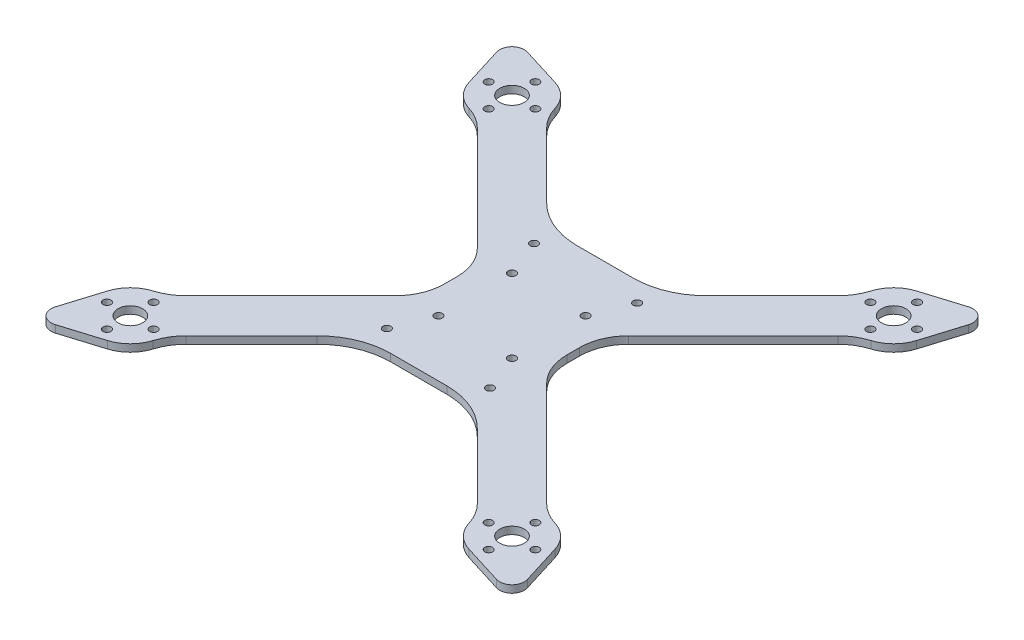
SolidWorks part; units mm, degrees
ref_plane "Front Plane" through (0, 0, 0) normal (0, 0, 1) x (1, 0, 0)
ref_plane "Top Plane" through (0, 0, 0) normal (0, 1, 0) x (1, 0, 0)
ref_plane "Right Plane" through (0, 0, 0) normal (1, 0, 0) x (0, 0, -1)
sketch "Sketch1" plane through (0, 0, 0) normal (0, 1, 0) x (1, 0, 0)
  line L0 (0, 110) -> (0, -110) construction
  line L1 (0, 0) -> (-77.7817, -77.7817) construction
  line L2 (0, 0) -> (-77.7817, 77.7817) construction
  line L3 (-77.7817, -77.7817) -> (-98.9949, -98.9949) construction
  line L4 (-11.4315, 38) -> (11.4315, 38)
  line L6 (-11.4315, -38) -> (11.4315, -38)
  line L7 (25, 2.5736) -> (25, -2.5736)
  line L8 (-15, 15) -> (15, 15) construction
  line L10 (-15, -15) -> (15, -15) construction
  line L11 (15, 15) -> (15, -15) construction
  line L12 (32.6447, 46.7868) -> (59.397, 73.5391)
  line L13 (30.8579, 16.7157) -> (73.5391, 59.397)
  line L14 (32.6447, -46.7868) -> (59.397, -73.5391)
  line L15 (30.8579, -16.7157) -> (73.5391, -59.397)
  line L16 (77.7817, 77.7817) -> (98.9949, 98.9949) construction
  line L17 (77.7817, -77.7817) -> (98.9949, -98.9949) construction
  line L18 (73.6461, -91.157) -> (89.9418, -96.1957)
  line L19 (96.1957, -89.9418) -> (91.157, -73.6461)
  line L20 (89.9418, 96.1957) -> (73.6461, 91.157)
  line L21 (96.1957, 89.9418) -> (91.157, 73.6461)
  line L22 (0, 0) -> (77.7817, 77.7817) construction
  line L23 (-77.7817, 77.7817) -> (-98.9949, 98.9949) construction
  line L24 (0, 0) -> (77.7817, -77.7817) construction
  line L25 (-15, 15) -> (-15, -15) construction
  line L26 (-96.1957, 89.9418) -> (-91.157, 73.6461)
  line L27 (-89.9418, 96.1957) -> (-73.6461, 91.157)
  line L28 (-96.1957, -89.9418) -> (-91.157, -73.6461)
  line L29 (-73.6461, -91.157) -> (-89.9418, -96.1957)
  line L30 (-30.8579, -16.7157) -> (-73.5391, -59.397)
  line L31 (-32.6447, -46.7868) -> (-59.397, -73.5391)
  line L32 (-30.8579, 16.7157) -> (-73.5391, 59.397)
  line L33 (-32.6447, 46.7868) -> (-59.397, 73.5391)
  line L34 (-25, 2.5736) -> (-25, -2.5736)
  line L35 (0, 0) -> (25, 0) construction
  circle A1 centre (77.7817, 77.7817) radius 63.5 construction
  circle A2 centre (77.7817, -77.7817) radius 63.5 construction
  circle A5 centre (77.7817, 77.7817) radius 9.5 construction
  circle A9 centre (77.7817, 68.2817) radius 1.6
  circle A10 centre (68.2817, 77.7817) radius 1.6
  circle A11 centre (77.7817, 87.2817) radius 1.6
  circle A12 centre (87.2817, 77.7817) radius 1.6
  circle A13 centre (77.7817, -87.2817) radius 1.6
  circle A14 centre (77.7817, -77.7817) radius 9.5 construction
  circle A15 centre (68.2817, -77.7817) radius 1.6
  circle A16 centre (77.7817, -68.2817) radius 1.6
  circle A17 centre (87.2817, -77.7817) radius 1.6
  circle A19 centre (-77.7817, -77.7817) radius 9.5 construction
  circle A24 centre (-77.7817, 77.7817) radius 9.5 construction
  arc A28 (81.858, 64.3883) -> (91.157, 73.6461) centre (77.7817, 77.7817) ccw
  arc A29 (64.3883, -81.858) -> (73.6461, -91.157) centre (77.7817, -77.7817) ccw
  arc A30 (73.6461, 91.157) -> (64.3883, 81.858) centre (77.7817, 77.7817) ccw
  arc A31 (91.157, -73.6461) -> (81.858, -64.3883) centre (77.7817, -77.7817) ccw
  arc A32 (73.5391, -59.397) -> (81.858, -64.3883) centre (87.6812, -45.2548) ccw
  arc A33 (59.397, -73.5391) -> (64.3883, -81.858) centre (45.2548, -87.6812) cw
  arc A34 (81.858, 64.3883) -> (73.5391, 59.397) centre (87.6812, 45.2548) ccw
  arc A35 (59.397, 73.5391) -> (64.3883, 81.858) centre (45.2548, 87.6812) ccw
  arc A36 (96.1957, 89.9418) -> (89.9418, 96.1957) centre (91.4188, 91.4188) ccw
  arc A37 (96.1957, -89.9418) -> (89.9418, -96.1957) centre (91.4188, -91.4188) cw
  arc A38 (32.6447, -46.7868) -> (11.4315, -38) centre (11.4315, -68) ccw
  arc A39 (11.4315, 38) -> (32.6447, 46.7868) centre (11.4315, 68) ccw
  arc A40 (30.8579, -16.7157) -> (25, -2.5736) centre (45, -2.5736) cw
  arc A41 (25, 2.5736) -> (30.8579, 16.7157) centre (45, 2.5736) cw
  circle A42 centre (15, 15) radius 1.6
  circle A43 centre (15, -15) radius 1.6
  circle A44 centre (77.7817, 77.7817) radius 5
  circle A45 centre (77.7817, -77.7817) radius 5
  circle A46 centre (-77.7817, -77.7817) radius 63.5 construction
  circle A47 centre (0, 0) radius 110 construction
  circle A48 centre (-77.7817, 77.7817) radius 63.5 construction
  circle A49 centre (-87.2817, -77.7817) radius 1.6 [skipped]
  circle A50 centre (-77.7817, -68.2817) radius 1.6 [skipped]
  circle A51 centre (-68.2817, -77.7817) radius 1.6 [skipped]
  circle A52 centre (-77.7817, -87.2817) radius 1.6 [skipped]
  circle A53 centre (-77.7817, 87.2817) radius 1.6 [skipped]
  circle A54 centre (-68.2817, 77.7817) radius 1.6 [skipped]
  circle A55 centre (-77.7817, 68.2817) radius 1.6 [skipped]
  circle A56 centre (-87.2817, 77.7817) radius 1.6 [skipped]
  circle A57 centre (-77.7817, -77.7817) radius 9.5 construction
  circle A58 centre (-77.7817, 77.7817) radius 9.5 construction
  circle A59 centre (-77.7817, -77.7817) radius 5
  circle A60 centre (-77.7817, 77.7817) radius 5
  circle A61 centre (-15, -15) radius 1.6
  circle A62 centre (-15, 15) radius 1.6
  arc A63 (-25, 2.5736) -> (-30.8579, 16.7157) centre (-45, 2.5736) ccw
  arc A64 (-30.8579, -16.7157) -> (-25, -2.5736) centre (-45, -2.5736) ccw
  arc A65 (-11.4315, 38) -> (-32.6447, 46.7868) centre (-11.4315, 68) cw
  arc A66 (-32.6447, -46.7868) -> (-11.4315, -38) centre (-11.4315, -68) cw
  arc A67 (-96.1957, -89.9418) -> (-89.9418, -96.1957) centre (-91.4188, -91.4188) ccw
  arc A68 (-96.1957, 89.9418) -> (-89.9418, 96.1957) centre (-91.4188, 91.4188) cw
  arc A69 (-59.397, 73.5391) -> (-64.3883, 81.858) centre (-45.2548, 87.6812) cw
  arc A70 (-81.858, 64.3883) -> (-73.5391, 59.397) centre (-87.6812, 45.2548) cw
  arc A71 (-59.397, -73.5391) -> (-64.3883, -81.858) centre (-45.2548, -87.6812) ccw
  arc A72 (-73.5391, -59.397) -> (-81.858, -64.3883) centre (-87.6812, -45.2548) cw
  arc A73 (-91.157, -73.6461) -> (-81.858, -64.3883) centre (-77.7817, -77.7817) cw
  arc A74 (-73.6461, 91.157) -> (-64.3883, 81.858) centre (-77.7817, 77.7817) cw
  arc A75 (-64.3883, -81.858) -> (-73.6461, -91.157) centre (-77.7817, -77.7817) cw
  arc A76 (-81.858, 64.3883) -> (-91.157, 73.6461) centre (-77.7817, 77.7817) cw
  circle A77 centre (-87.2817, -77.7817) radius 1.6
  circle A78 centre (-77.7817, -68.2817) radius 1.6
  circle A79 centre (-68.2817, -77.7817) radius 1.6
  circle A80 centre (-77.7817, -87.2817) radius 1.6
  circle A81 centre (-87.2817, 77.7817) radius 1.6
  circle A82 centre (-77.7817, 87.2817) radius 1.6
  circle A83 centre (-68.2817, 77.7817) radius 1.6
  circle A84 centre (-77.7817, 68.2817) radius 1.6
  circle A89 centre (-21, 30) radius 1.6
  circle A90 centre (-21, -30) radius 1.6
  circle A91 centre (21, -30) radius 1.6
  circle A92 centre (21, 30) radius 1.6
  point P16 (-77.7817, 77.7817)
  point P34 (77.7817, 77.7817)
  point P49 (0, -15)
  point P50 (0, 15)
  point P65 (0, 0)
  point P89 (0, 38)
  point P160 (0, -38)
  dimension "D3" = 38
  dimension "D9" = 4
  dimension "D17" = 20
  dimension "D18" = 5
  dimension "D19" = 30
  dimension "D20" = 20
  dimension "D5" = 21
  dimension "D6" = 30
  dimension "D7" = 30
  dimension "D8" = 21
  dimension "D2" = 25
  dimension "D4" = 38
  dimension "D15" = 30
  dimension "D16" = 30
  dimension "D10" = 4
extrude "Boss-Extrude1" add sketch "Sketch1" along normal blind 3
